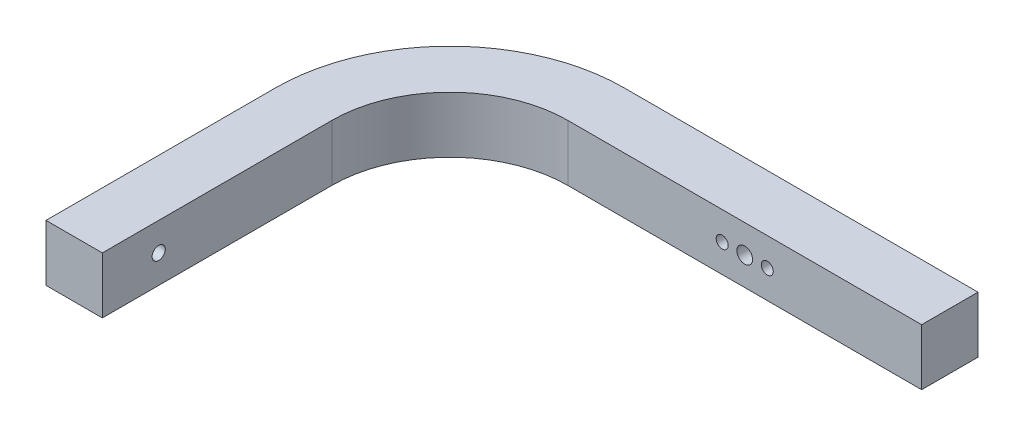
SolidWorks part; units mm, degrees
ref_plane "Front Plane" through (0, 0, 0) normal (0, 0, 1) x (1, 0, 0)
ref_plane "Top Plane" through (0, 0, 0) normal (0, 1, 0) x (1, 0, 0)
ref_plane "Right Plane" through (0, 0, 0) normal (1, 0, 0) x (0, 0, -1)
ref_axis "Z" through (0, 0, -5.375) along (0, 0, 1)
sketch "Sketch1" plane through (0, 0, 0) normal (0, 1, 0) x (1, 0, 0)
  line L0 (-47.1, 0) -> (47.1, 0)
  line L1 (-93.5, -46.4) -> (-93.5, -107.5)
  line L2 (-93.5, -107.5) -> (-78.5, -107.5)
  line L3 (-78.5, -107.5) -> (-78.5, -46.4)
  line L4 (-47.1, -15) -> (47.1, -15)
  line L5 (0, -15) -> (0, 0) construction
  line L6 (78.5, -107.5) -> (78.5, -46.4) construction
  line L7 (93.5, -107.5) -> (78.5, -107.5) construction
  line L8 (93.5, -46.4) -> (93.5, -107.5) construction
  line L9 (47.1, 0) -> (47.1, -15)
  arc A0 (-47.1, 0) -> (-93.5, -46.4) centre (-47.1, -46.4) ccw
  arc A1 (-78.5, -46.4) -> (-47.1, -15) centre (-47.1, -46.4) cw
  arc A2 (78.5, -46.4) -> (47.1, -15) centre (47.1, -46.4) ccw construction
  arc A3 (47.1, 0) -> (93.5, -46.4) centre (47.1, -46.4) cw construction
  dimension "D3" = 31.4
  dimension "D1" = 157
  dimension "D2" = 15
  dimension "D4" = 92.5
extrude "Boss-Extrude1" add sketch "Sketch1" along normal blind 7.5 and the other way blind 7.5
sketch "Sketch2" plane through (-78.5, 0, 0) normal (-1, 0, 0) x (0, 0, 1)
  line L1 (59.125, 0) -> (-59.125, 0) construction
  line L2 (0, -8.25) -> (0, 8.25) construction
  circle A0 centre (92.5, 0) radius 1.75
  dimension "D1" = 3.5
  dimension "D2" = 92.5
extrude "Cut-Extrude1" cut sketch "Sketch2" against normal through all both and the other way through all
ref_axis "Axis2" through (-120.1767, 0, 92.5) along (1, 0, 0)
sketch "Sketch3" plane through (0, 0, 0) normal (0, 0, -1) x (-1, 0, 0)
  line L0 (-6, 0) -> (6, 0) construction
  circle A0 centre (0, 0) radius 2.1
  circle A1 centre (-6, 0) radius 1.6
  circle A2 centre (6, 0) radius 1.6
  dimension "D1" = 4.2
  dimension "D3" = 3.2
  dimension "D2" = 12
extrude "Cut-Extrude2" cut sketch "Sketch3" against normal through all
sketch "Sketch4" plane through (-93.5, 0, 0) normal (1, 0, 0) x (0, 0, -1)
  circle A0 centre (-92.5, 0) radius 2.275
  circle A1 centre (-92.5, 0) radius 1.75 construction
  dimension "D1" = 4.55
extrude "Cut-Extrude3" cut sketch "Sketch4" along normal blind 6
sketch "Sketch5" plane through (-93.5, 0, 0) normal (-1, 0, 0) x (0, 0, 1)
  circle A0 centre (92.5, 0) radius 3.825
  dimension "D1" = 7.65
extrude "Cut-Extrude4" cut sketch "Sketch5" against normal blind 0.75
equation "\"width\"= \"EyeDiameter\" + \"EyeClearance\""
equation "\"prongwidth\"= \"L2Thickness\""
equation "\"D2@Sketch1\"=\"prongwidth\""
equation "\"D3@Sketch1\"=\"width\"/5"
equation "\"pronglength\"= \"BasePlaneDistance\"'model implicitly adds clearance (of prongwidth) to the hole drilled at the baseplanedistance"
equation "\"D4@Sketch1\"=\"pronglength\""
equation "\"D1@Boss-Extrude1\"=\"prongwidth\"/2"
equation "\"D2@Boss-Extrude1\"=\"prongwidth\"/2"
equation "\"lbracket-plane-to-axis\"= \"BasePlaneDistance\""
equation "\"D2@Sketch2\"=\"lbracket-plane-to-axis\""
equation "\"EyeDiameter\" = 155"
equation "\"BasePlaneDistance\" = \"EyeDiameter\"/2+15"
equation "\"EyeClearance\" = 2"
equation "\"D1@Sketch1\"=\"EyeDiameter\"+\"EyeClearance\""
equation "\"BearingDepth\"= 6"
equation "\"BearingHousingID\"=4.5"
equation "\"D1@Sketch4\"=\"BearingHousingID\" + \"PrinterFilamentThickness\" * \"ApplyPrinterOffset\" / 2"
equation "\"D1@Cut-Extrude3\"=\"BearingDepth\""
equation "\"BearingFlangeThickness\"= 0.75"
equation "\"BearingFlangeOD\"=7.5"
equation "\"D1@Sketch5\"=\"BearingFlangeOD\" + \"PrinterFilamentThickness\"*1.5 *\"ApplyPrinterOffset\""
equation "\"D1@Cut-Extrude4\"=\"BearingFlangeThickness\""
equation "\"PrinterFilamentThickness\"= 0.1"
equation "\"ApplyPrinterOffset\"= 1'if 1, adjust hole sizes to try and make pressfits work with the 3d printer"
equation "\"L2Thickness\" = 15"
equation "\"L2_ID\" = 20"
equation "\"vx\" = -3"
equation "\"vy\" = 3"
equation "\"vz\" = 10"
equation "\"parametric_end\" = 1"
equation "\"Rw_3_xx\" = -(\"vz\")/sqr((\"vx\")^2 + (\"vz\")^2)"
equation "\"Rw_3_xy\" = 0"
equation "\"Rw_3_xz\" = (\"vx\")/sqr((\"vx\")^2 + (\"vz\")^2)"
equation "\"Rw_3_zx\" = (\"vx\")/sqr((\"vx\")^2 + (\"vy\")^2 + (\"vz\")^2)"
equation "\"Rw_3_zy\" = (\"vy\")/sqr((\"vx\")^2 + (\"vy\")^2 + (\"vz\")^2)"
equation "\"Rw_3_zz\" = (\"vz\")/sqr((\"vx\")^2 + (\"vy\")^2 + (\"vz\")^2)"
equation "\"Rw_3_yx\" = (\"vx\")*(\"vy\")/sqr((\"vx\")^4 + (\"vx\")^2*(\"vy\")^2 + 2*(\"vx\")^2*(\"vz\")^2 + (\"vy\")^2*(\"vz\")^2 + (\"vz\")^4)"
equation "\"Rw_3_yy\" = -sqr((\"vx\")^2 + (\"vz\")^2)/sqr((\"vx\")^2 + (\"vy\")^2 + (\"vz\")^2)"
equation "\"Rw_3_yz\" = (\"vy\")*(\"vz\")/sqr((\"vx\")^4 + (\"vx\")^2*(\"vy\")^2 + 2*(\"vx\")^2*(\"vz\")^2 + (\"vy\")^2*(\"vz\")^2 + (\"vz\")^4)"
equation "\"O2Targx\" = -\"BasePlaneDistance\"*(\"vx\")*(\"vy\")/sqr((\"vx\")^4 + (\"vx\")^2*(\"vy\")^2 + 2*(\"vx\")^2*(\"vz\")^2 + (\"vy\")^2*(\"vz\")^2 + (\"vz\")^4)"
equation "\"O2Targy\" = \"BasePlaneDistance\"*sqr((\"vx\")^2 + (\"vz\")^2)/sqr((\"vx\")^2 + (\"vy\")^2 + (\"vz\")^2)"
equation "\"O2Targz\" = -\"BasePlaneDistance\"*(\"vy\")*(\"vz\")/sqr((\"vx\")^4 + (\"vx\")^2*(\"vy\")^2 + 2*(\"vx\")^2*(\"vz\")^2 + (\"vy\")^2*(\"vz\")^2 + (\"vz\")^4)"
equation "\"O2Targx_0\" = -(\"BasePlaneDistance\")*sqr((\"vx\")^2 + (\"vz\")^2)/sqr((\"vx\")^2 + (\"vy\")^2 + (\"vz\")^2)"
equation "\"O2Targy_0\" = -(\"BasePlaneDistance\")*(\"vy\")*(\"vz\")/sqr((\"vx\")^4 + (\"vx\")^2*(\"vy\")^2 + 2*(\"vx\")^2*(\"vz\")^2 + (\"vy\")^2*(\"vz\")^2 + (\"vz\")^4)"
equation "\"O2Targz_0\" = (\"BasePlaneDistance\")*(\"vx\")*(\"vy\")/sqr((\"vx\")^4 + (\"vx\")^2*(\"vy\")^2 + 2*(\"vx\")^2*(\"vz\")^2 + (\"vy\")^2*(\"vz\")^2 + (\"vz\")^4) + (\"BasePlaneDistance\")"
equation "\"theta2_s1\" = arcsin(((\"BasePlaneDistance\") - (\"O2Targz_0\"))/(\"BasePlaneDistance\")) + pi"
equation "\"theta2_s2\" = -arcsin(((\"BasePlaneDistance\") - (\"O2Targz_0\"))/(\"BasePlaneDistance\"))"
equation "\"theta1_s1\" = arcsin((\"O2Targy_0\")/((\"BasePlaneDistance\")*cos((\"Theta2\")))) + pi"
equation "\"theta1_s2\" = -arcsin((\"O2Targy_0\")/((\"BasePlaneDistance\")*cos((\"Theta2\"))))"
equation "\"theta1_s3\" = -arccos(-(\"O2Targx_0\")/((\"BasePlaneDistance\")*cos((\"Theta2\")))) + 2*pi"
equation "\"theta1_s4\" = arccos(-(\"O2Targx_0\")/((\"BasePlaneDistance\")*cos((\"Theta2\"))))"
equation "\"Theta1\" = \"theta1_s2\" 'so far, theta1_s1 and theta1_s4 have agreed, and they agree with the sw constraint solver"
equation "\"Theta2\" = \"theta2_s2\""
equation "\"o2_x\" = -(\"BasePlaneDistance\")*cos((\"Theta1\"))*cos((\"Theta2\"))"
equation "\"o2_y\" = -(\"BasePlaneDistance\")*sin((\"Theta1\"))*cos((\"Theta2\"))"
equation "\"o2_z\" = (\"BasePlaneDistance\")*(sin((\"Theta2\")) + 1)"
equation "\"o1_x\" = (\"BasePlaneDistance\")*sin((\"Theta1\"))"
equation "\"o1_y\" = -(\"BasePlaneDistance\")*cos((\"Theta1\"))"
equation "\"o1_z\" = (\"BasePlaneDistance\")"
equation "\"Actuator1_Theta\" = atn(\"vx\"/\"vz\") 'ik solution for the single link joint"
equation "\"Actuator2_Theta\" = \"Theta1\"  'ik solution for the double link joint"
